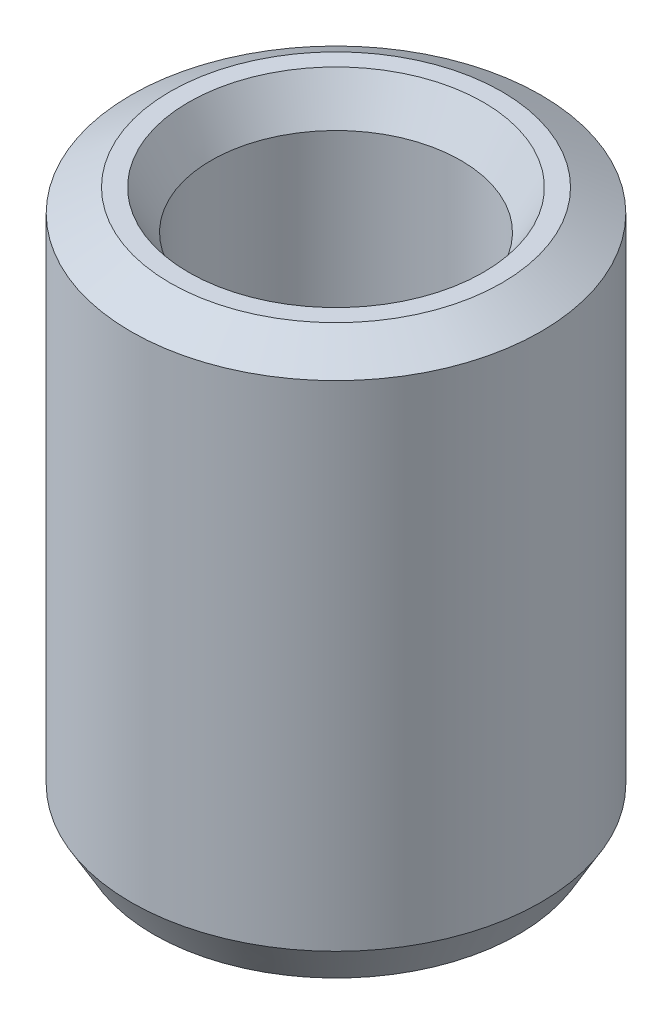
SolidWorks part; units mm, degrees
ref_plane "Front Plane" through (0, 0, 0) normal (0, 0, 1) x (1, 0, 0)
ref_plane "Top Plane" through (0, 0, 0) normal (0, 1, 0) x (1, 0, 0)
ref_plane "Right Plane" through (0, 0, 0) normal (1, 0, 0) x (0, 0, -1)
sketch "Sketch1" plane through (0, 0, 0) normal (0, 1, 0) x (1, 0, 0)
  circle A0 centre (0, 0) radius 17.5
  dimension "SLEEVE_OD" = 35
extrude "Boss-Extrude1" add sketch "Sketch1" along normal blind 47.4702
sketch "Sketch2" plane through (0, 0, 0) normal (0, 1, 0) x (1, 0, 0)
  circle A0 centre (0, 0) radius 10.6592
  dimension "BORE_D" = 21.3184
extrude "Cut-Extrude1" cut sketch "Sketch2" along normal through all
chamfer "Chamfer1" distance 1.9271 angle 60 4 edges at (0, 47.4702, 10.6592) (0, 0, 10.6592) (0, 0, 17.5) (0, 47.4702, 17.5) first distance on face at (0, 47.4702, 10.6592) first distance on face at (0, 0, 10.6592) first distance on face at (0, 47.4702, 17.5)
